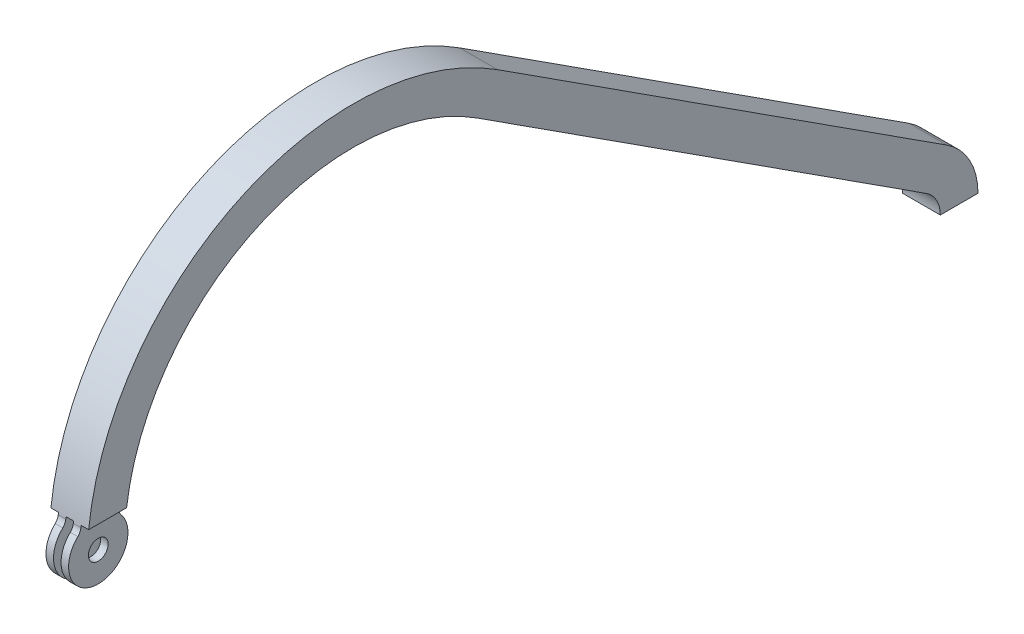
SolidWorks part; units mm, degrees
ref_plane "Front Plane" through (0, 0, 0) normal (0, 0, 1) x (1, 0, 0)
ref_plane "Top Plane" through (0, 0, 0) normal (0, 1, 0) x (1, 0, 0)
ref_plane "Right Plane" through (0, 0, 0) normal (1, 0, 0) x (0, 0, -1)
sketch "Sketch1" plane through (0, 0, 0) normal (1, 0, 0) x (0, 0, -1)
  line L0 (0, 0) -> (862.5, 0) construction
  line L1 (862.5, 0) -> (862.5, -164.7369) construction
  line L2 (0, 0) -> (0, 125) construction
  circle A0 centre (0, 125) radius 10
  circle A1 centre (0, 125) radius 30
  dimension "D3" = 20
  dimension "D4" = 60
  dimension "D1" = 862.5
  dimension "D2" = 125
sketch "Sketch2" plane through (0, 0, 0) normal (1, 0, 0) x (0, 0, -1)
  line L0 (839.6134, 42.0103) -> (385.567, 335.0514)
  line L1 (862.5, 0) -> (862.5, -164.7369) construction
  line L2 (0, 0) -> (0, 125) construction
  arc A0 (839.6134, 42.0103) -> (862.5, 0) centre (812.5, 0) cw
  arc A1 (385.567, 335.0514) -> (0, 125) centre (250, 125) ccw
  dimension "D1" = 50
  dimension "D2" = 250
sketch "Sketch3" plane through (0, 0, 0) normal (0, 1, 0) x (1, 0, 0)
  line L0 (0, 0) -> (0, 862.5) construction
  line L1 (-19.05, 843.45) -> (19.05, 843.45)
  line L2 (-19.05, 843.45) -> (-19.05, 881.55)
  line L3 (-19.05, 881.55) -> (19.05, 881.55)
  line L4 (19.05, 843.45) -> (19.05, 881.55)
  line L5 (-19.05, 843.45) -> (19.05, 881.55) construction
  line L6 (-19.05, 881.55) -> (19.05, 843.45) construction
  line L7 (0, 0) -> (0, 862.5) construction
  point P0 (0, 862.5)
  dimension "D1" = 38.1
sweep "Sweep1" add profiles "Sketch3" path "Sketch2"
sketch "Sketch4" plane through (19.05, 0, 0) normal (1, 0, 0) x (0, 0, -1)
  line L4 (843.45, 0) -> (881.55, 0)
  line L5 (849.9436, 58.0162) -> (395.8972, 351.0573)
  line L6 (-19.05, 125) -> (19.05, 125)
  line L7 (375.2368, 319.0455) -> (829.2832, 26.0044)
  line L8 (843.45, 0) -> (881.55, 0)
  line L9 (849.9436, 58.0162) -> (395.8972, 351.0573)
  line L10 (-19.05, 125) -> (19.05, 125)
  line L11 (375.2368, 319.0455) -> (829.2832, 26.0044)
  circle A0 centre (0, 125) radius 30 construction
  circle A1 centre (0, 125) radius 10 construction
  arc A2 (-20.6534, 146.7587) -> (22.9216, 144.3545) centre (0, 125) ccw
  circle A3 centre (0, 125) radius 10
  arc A4 (20.6306, 151.974) -> (22.9216, 144.3545) centre (30.5622, 150.8061) ccw
  arc A5 (-20.6534, 146.7587) -> (-17.592, 152.9719) centre (-27.5378, 154.0115) ccw
  arc A8 (843.45, 0) -> (829.2832, 26.0044) centre (812.5, 0) ccw
  arc A9 (881.55, 0) -> (849.9436, 58.0162) centre (812.5, 0) ccw
  arc A10 (395.8972, 351.0573) -> (-19.05, 125) centre (250, 125) ccw
  arc A11 (375.2368, 319.0455) -> (19.05, 125) centre (250, 125) ccw
  arc A12 (843.45, 0) -> (829.2832, 26.0044) centre (812.5, 0) ccw
  arc A13 (881.55, 0) -> (849.9436, 58.0162) centre (812.5, 0) ccw
  arc A14 (395.8972, 351.0573) -> (-17.592, 152.9719) centre (250, 125) ccw
  arc A15 (375.2368, 319.0455) -> (20.6306, 151.974) centre (250, 125) ccw
  arc M13 (395.8972, 351.0573) -> (-19.05, 125) centre (250, 125) ccw
  line M14 (-19.05, 125) -> (19.05, 125)
  arc M15 (19.05, 125) -> (375.2368, 319.0455) centre (250, 125) cw
  dimension "D2" = 10
  dimension "D1" = 0
extrude "Boss-Extrude2" add sketch "Sketch4" against normal up to surface (38.1 mm away) contours A5 A2 A4 A3 M15 M14 M13 region at (19.05, 147.6864, -20.1867)
sketch "Sketch5" plane through (19.05, 0, 0) normal (1, 0, 0) x (0, 0, -1)
  circle A0 centre (0, 125) radius 10 construction
  circle A1 centre (0, 125) radius 10
extrude "Cut-Extrude1" cut sketch "Sketch5" against normal through all
ref_plane "Plane1" through (0, 95, 0) normal (0, -1, 0) x (-1, 0, 0)
sketch "Sketch7" plane through (0, 95, 0) normal (0, -1, 0) x (-1, 0, 0)
  line L0 (-19.05, 30) -> (-19.05, -30) construction
  line L1 (19.05, -58.9137) -> (-19.05, -58.9137)
  line L2 (19.05, -58.9137) -> (19.05, 57.4272)
  line L3 (19.05, 57.4272) -> (-19.05, 57.4272)
  line L4 (-19.05, -58.9137) -> (-19.05, 57.4272)
  line L5 (19.05, -30) -> (19.05, 30) construction
  line L6 (-19.05, -0.7433) -> (-11.43, -0.7433) construction
  line L7 (-11.43, 57.4272) -> (-3.81, 57.4272)
  line L8 (-11.43, 57.4272) -> (-11.43, -58.9137)
  line L9 (-11.43, -58.9137) -> (-3.81, -58.9137)
  line L10 (-3.81, 57.4272) -> (-3.81, -58.9137)
  line L11 (3.81, 57.4272) -> (11.43, 57.4272)
  line L12 (3.81, 57.4272) -> (3.81, -58.9137)
  line L13 (3.81, -58.9137) -> (11.43, -58.9137)
  line L14 (11.43, 57.4272) -> (11.43, -58.9137)
  line L15 (-11.43, -0.7433) -> (-3.81, -0.7433) construction
  line L16 (-3.81, -0.7433) -> (3.81, -0.7433) construction
  line L17 (3.81, -0.7433) -> (11.43, -0.7433) construction
  line L18 (11.43, -0.7433) -> (19.05, -0.7433) construction
extrude "Cut-Extrude2" cut sketch "Sketch7" against normal blind 60 contours L8 L3 L4 L1 | L12 L3 L10 L1 | L3 L14 L1 L2 region at (-15.24, 95, 0.7433) region at (0, 95, 0.7433) region at (15.24, 95, 0.7433)
ref_plane "Plane2" through (0, 394.05, 0) normal (0, 1, 0) x (1, 0, 0)
ref_point "Point1"
ref_axis "Axis1" through (0, 0, -862.5) along (0, -1, 0)
